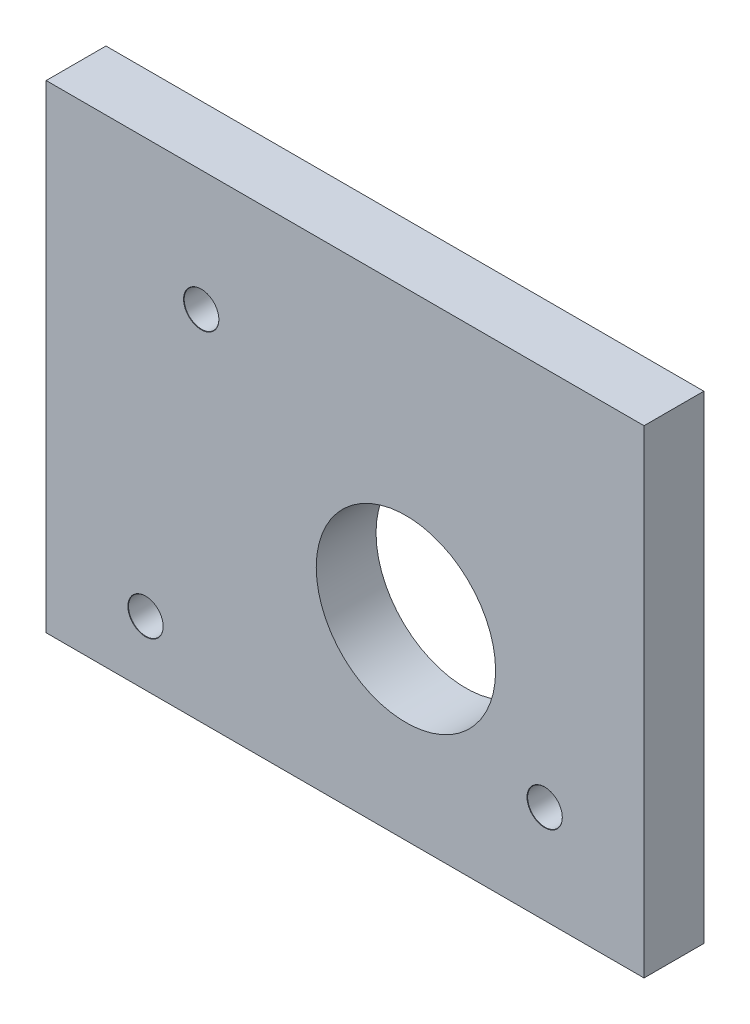
SolidWorks part; units mm, degrees
ref_plane "Front Plane" through (0, 0, 0) normal (0, 0, 1) x (1, 0, 0)
ref_plane "Top Plane" through (0, 0, 0) normal (0, 1, 0) x (1, 0, 0)
ref_plane "Right Plane" through (0, 0, 0) normal (1, 0, 0) x (0, 0, -1)
sketch "hole_reference" plane through (0, 0, 0) normal (0, 0, 1) x (1, 0, 0)
  line L0 (0, 0) -> (33.3777, 0) construction
  line L1 (33.3777, 0) -> (33.3777, 2.86) construction
  point P0 (0, 0)
  point P1 (33.3777, 2.86)
  point P3 (4.6551, 24.5628)
  point P4 (21.7754, 10.6949)
  dimension "D1" = 33.5
  dimension "D2" = 25
  dimension "D3" = 36
  dimension "D4" = 2.86
  dimension "D5" = 14
  dimension "D6" = 24.26
sketch "Sketch1" plane through (0, 0, 0) normal (0, 0, 1) x (1, 0, 0)
  line L0 (4.6551, 24.5628) -> (4.6551, 0) construction
  line L1 (-8.3112, 34.6544) -> (41.6888, 34.6544)
  line L2 (-8.3112, 34.6544) -> (-8.3112, -5.3456)
  line L3 (-8.3112, -5.3456) -> (41.6888, -5.3456)
  line L4 (41.6888, 34.6544) -> (41.6888, -5.3456)
  line L5 (0, 0) -> (33.3777, 0) construction
  line L8 (16.6888, 0) -> (16.6888, -5.3456) construction
  dimension "D1" = 40
  dimension "D2" = 50
  dimension "D3" = 10.0916
extrude "Boss-Extrude1" add sketch "Sketch1" along normal mid plane 5 contours L1 L4 L3 L2
hole_wizard "M2.5 Clearance Hole2" positions "Sketch2" profile "Sketch3" hole size "M2.5" standard "ANSI Metric" end condition through all
sketch "Sketch2" plane through (0, 0, 2.5) normal (0, 0, 1) x (1, 0, 0)
  point P0 (4.6551, 24.5628)
  point P6 (33.3777, 2.86)
  point P19 (0, 0)
sketch "Sketch3" plane through (4.6551, 24.5628, 2.5) normal (1, 0, 0) x (0, -1, 0)
  line L0 (0, 0) -> (0, 5)
  line L1 (0, 5) -> (1.45, 5)
  line L2 (1.45, 5) -> (1.45, 0.025)
  line L3 (1.45, 0.025) -> (1.475, 0)
  line L5 (1.475, 0) -> (0, 0)
  line L6 (-1.45, 0.025) -> (-1.475, 0) construction
  line L11 (0, -6.35) -> (0, 107.95) construction
  dimension "Thru Hole Dia." = 2.9
  dimension "Thru Hole Depth" = 5
  dimension "Near C'Sink Dia." = 2.95
  dimension "Near C'Sink Angle" = 90
sketch "Sketch4" plane through (0, 0, 2.5) normal (0, 0, 1) x (1, 0, 0)
  circle A0 centre (21.7754, 10.6949) radius 7.5
  dimension "D1" = 15
extrude "Cut-Extrude1" cut sketch "Sketch4" against normal through all
ref_axis "Axis1" through (21.7754, 10.6949, -2.5) along (0, 0, 1)
ref_plane "Plane1" through (0, 10.6949, 0) normal (0, -1, 0) x (-1, 0, 0)
ref_plane "Plane2" through (21.7754, 0, 0) normal (1, 0, 0) x (0, 0, -1)
